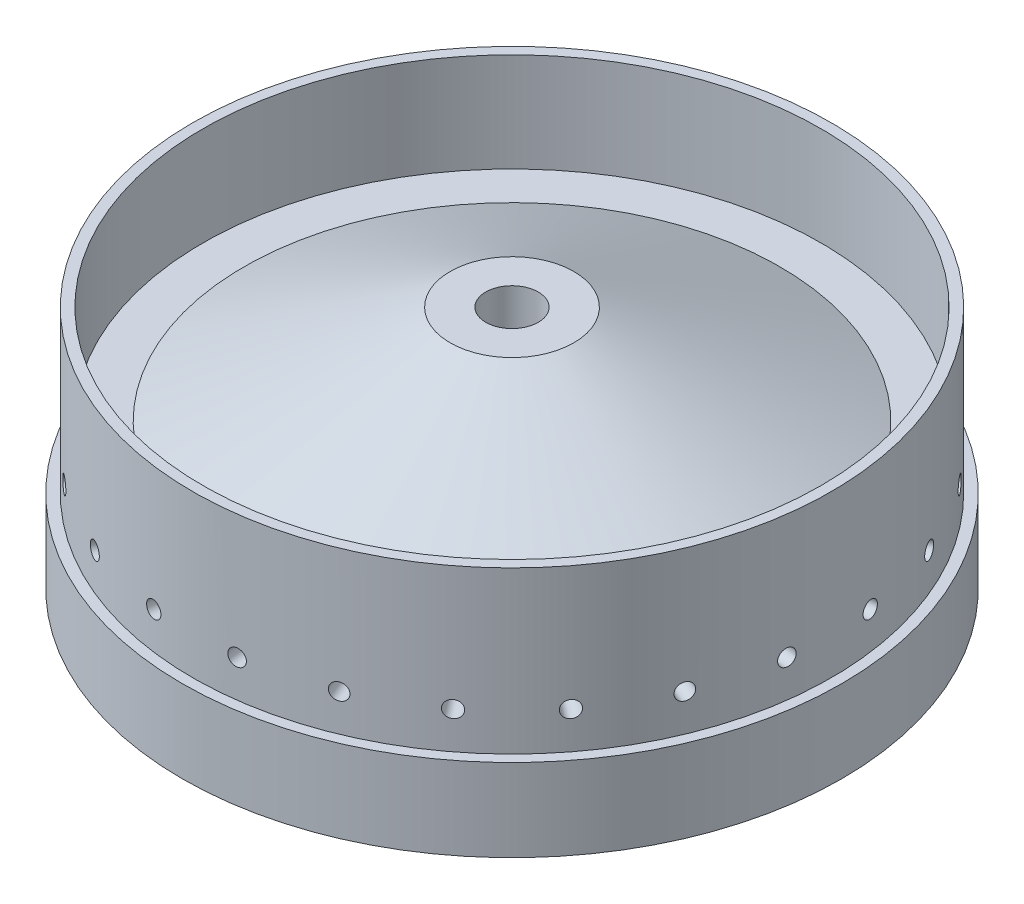
SolidWorks part; units mm, degrees
material "6061-T4 (SS)"
ref_plane "Front Plane" through (0, 0, 0) normal (0, 0, 1) x (1, 0, 0)
ref_plane "Top Plane" through (0, 0, 0) normal (0, 1, 0) x (1, 0, 0)
ref_plane "Right Plane" through (0, 0, 0) normal (1, 0, 0) x (0, 0, -1)
ref_plane "Plane1" through (0, 0, -75.0887) normal (0, 0, 1) x (1, 0, 0)
sketch "Sketch1" plane through (0, 0, 0) normal (0, 1, 0) x (1, 0, 0)
  line L1 (95.25, 0) -> (101.6, 0)
  line L2 (0, 0) -> (0, 61.9125) construction
  line L4 (101.6, 59.4931) -> (101.6, 0)
  line L6 (101.6, 59.4931) -> (8.0962, 59.4931) construction
  line L8 (0, 75.0887) -> (101.6, 75.0887)
  line L9 (101.6, 75.0887) -> (101.6, 59.4931)
  line L10 (8.0962, 0) -> (8.0962, 75.0887)
  line L11 (8.0962, 75.0887) -> (-8.0962, 75.0887)
  line L12 (-8.0962, 75.0887) -> (-8.0962, 0)
  line L13 (-8.0962, 0) -> (8.0962, 0)
  line L14 (8.0962, 59.4931) -> (0, 59.4931) construction
  line L15 (19.05, 75.0887) -> (82.55, 44.6088)
  line L16 (82.55, 44.6088) -> (95.25, 44.6088)
  line L17 (95.25, 44.6088) -> (95.25, 75.0887)
  ellipse E0 centre (0, 0) end of major axis (-95.25, 0) minor radius 59.4931
  point P18 (19.05, 75.0887)
  dimension "D4" = 15.5956
  dimension "D6" = 16.1925
  dimension "D7" = 6.35
  dimension "D8" = 30.48
  dimension "D9" = 12.7
  dimension "D10" = 19.05
  dimension "D2" = 101.6
  dimension "D3" = 75.0887
revolve "Revolve1" add sketch "Sketch1" angle 360 about L2 region at (66.7796, 0, -46.8658)
sketch "Sketch3" plane through (0, 0, 0) normal (0, 0, -1) x (-1, 0, 0)
  circle A0 centre (0, 0) radius 101.6
  circle A1 centre (0, 0) radius 98.425
  dimension "D1" = 203.2
  dimension "D2" = 3.175
extrude "Cut-Extrude2" cut sketch "Sketch3" along normal through all from offset 25.4
hole_wizard "1/4-20 Tapped Hole1" positions "3DSketch1" profile "Sketch10" tap size "1/4-20" standard "ANSI Inch"
sketch3d "3DSketch1"
  line L0 (97.583, 12.847, -36.83) -> (97.583, 12.847, 0) construction
  line L1 (97.583, 12.847, 0) -> (0, 0, 0) construction
  line L2 (0, 0, 0) -> (101.6, 0, 0) construction
  circle A0 centre (0, 0, 0) radius 101.6 construction
  point P0 (97.583, 12.847, -36.83)
  point P12 (0, 0, 101.6)
  dimension "D1" = 36.83
  dimension "D2" = 7.5
sketch "Sketch10" plane through (97.583, 12.847, -36.83) normal (0, 0, 1) x (-0.1305, 0.9914, 0)
  line L0 (0, 0) -> (0, 14.2338)
  line L1 (0, 14.2338) -> (2.5527, 12.7)
  line L2 (2.5527, 12.7) -> (2.5527, 0)
  line L5 (2.5527, 0) -> (0, 0)
  line L10 (0, 14.2338) -> (-2.5527, 12.7) construction
  line L11 (0, -6.35) -> (0, 107.95) construction
  dimension "Tap Drill Dia." = 5.1054
  dimension "Tap Drill Depth" = 12.7
  dimension "Drill Angle" = 118
cosmetic thread "Hole Thread2" parameters "D1"=12.7, "D2"=6.35
pattern_circular "CirPattern1" count 24 over 360 about axis through (0, 0, 0) along (0, 0, 1) of "1/4-20 Tapped Hole1"
sketch "Sketch13" plane through (0, 0, 0) normal (0, 0, 1) x (1, 0, 0)
  line L0 (-67.9108, -66.7883) -> (66.7883, 67.9108)
  line L1 (-66.7883, -67.9108) -> (67.9108, 66.7883)
  line L2 (0, 0) -> (0, -28.3739) construction
  circle A4 centre (0, 0) radius 95.25 construction
  arc A5 (-67.9108, -66.7883) -> (-66.7883, -67.9108) centre (0, 0) ccw
  arc A6 (66.7883, 67.9108) -> (67.9108, 66.7883) centre (0, 0) cw
  dimension "D1" = 1.5875
  dimension "D2" = 135
sketch "Sketch14" plane through (0, 0, -75.0888) normal (0, 0, -1) x (-1, 0, 0)
  circle A0 centre (0, 0) radius 8.0962
  circle A1 centre (0, 0) radius 8.0962 construction
move or copy body "Body-Move/Copy1" bodies to move or copy 120 copy no rotation origin (0, 0, -37.5444) rotation axis (1, 0, 0) rotation angle 90
equation "\"D7@Sketch1\"= .25"
equation "\"D1@Plane1\"= \"D3@Sketch1\""
